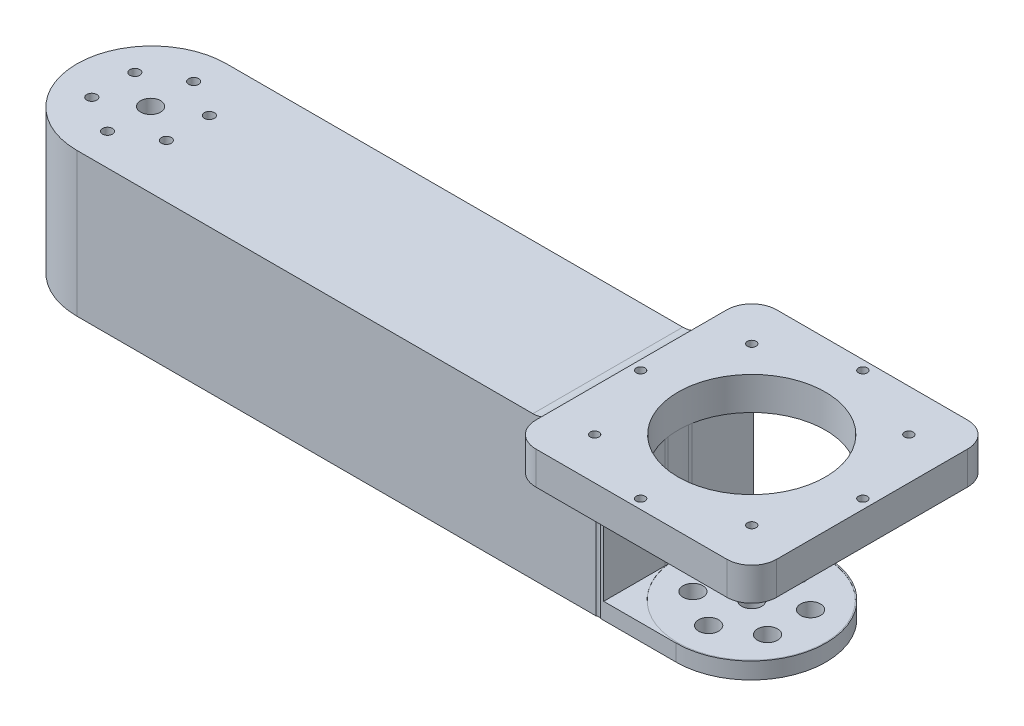
SolidWorks part; units mm, degrees
ref_plane "前视基准面" through (0, 0, 0) normal (0, 0, 1) x (1, 0, 0)
ref_plane "上视基准面" through (0, 0, 0) normal (0, 1, 0) x (1, 0, 0)
ref_plane "右视基准面" through (0, 0, 0) normal (1, 0, 0) x (0, 0, -1)
sketch "草图1" plane through (0, 0, 0) normal (0, 1, 0) x (1, 0, 0)
  line L0 (0, 0) -> (300, 0)
  line L1 (300, 0) -> (300, -60)
  line L2 (300, -60) -> (0, -60)
  line L3 (0, -60) -> (0, 0)
  dimension "D1" = 60
  dimension "D2" = 300
extrude "凸台-拉伸1" add sketch "草图1" along normal blind 57.52
fillet "圆角1" 2 edges at (0, 28.76, 0) (0, 28.76, 60) type full round first side face at (150, 28.76, 0) second side face at (150, 28.76, 60) middle face at (0, 28.76, 30)
sketch "草图3" plane through (300, 0, 0) normal (1, 0, 0) x (0, 0, -1)
  line L0 (0, 28.76) -> (-60, 28.76) construction
  line L1 (0, 57.52) -> (0, 0) construction
  line L2 (-60, 57.52) -> (-60, 0) construction
sketch "草图4" plane through (0, 57.52, 0) normal (0, 1, 0) x (1, 0, 0)
  circle A0 centre (29.5314, -29.9886) radius 29.5
  dimension "D1" = 59
sketch "草图9" plane through (300, 0, 0) normal (1, 0, 0) x (0, 0, -1)
  line L0 (-30, 57.52) -> (-30, 0) construction
  line L1 (-60, 57.52) -> (0, 57.52) construction
  line L2 (-60, 0) -> (0, 0) construction
  line L4 (-60, 50.92) -> (0, 50.92)
  line L5 (-60, 50.92) -> (-60, 6.6)
  line L6 (-60, 6.6) -> (0, 6.6)
  line L7 (0, 50.92) -> (0, 6.6)
  line L8 (-60, 50.92) -> (0, 6.6) construction
  line L9 (-60, 6.6) -> (0, 50.92) construction
  point P6 (-30, 28.76)
  dimension "D1" = 60
  dimension "D2" = 44.32
extrude "切除-拉伸5" cut sketch "草图9" against normal blind 59
fillet "圆角2" 2 edges at (300, 54.22, 60) (300, 54.22, 0) type full round first side face at (217.75, 28.76, 60) second side face at (217.75, 28.76, 0) middle face at (300, 54.22, 30)
fillet "圆角3" 2 edges at (300, 3.3, 60) (300, 3.3, 0) type full round first side face at (210.25, 28.76, 60) second side face at (210.25, 28.76, 0) middle face at (300, 3.3, 30)
sketch "草图10" plane through (0, 57.52, 0) normal (0, 1, 0) x (1, 0, 0)
  circle A0 centre (270.1322, -30.0374) radius 29.5
extrude "切除-拉伸6" cut sketch "草图10" against normal blind 51
fillet "圆角4" radius 10 2 edges at (241, 28.76, 25.3937) (241, 28.76, 34.6812)
sketch "草图16" plane through (0, 6.52, 0) normal (0, 1, 0) x (1, 0, 0)
  line L0 (300, -30) -> (240.6322, -30.0374) construction
  line L2 (300, 0) -> (300, -60) construction
  circle A0 centre (270.1322, -30.0374) radius 29.5 construction
  circle A1 centre (270.1322, -30.0374) radius 29.5 construction
  circle A2 centre (270.3161, -30.0187) radius 44.5 construction
  circle A3 centre (225.8161, -30.0187) radius 1.75
  dimension "D1" = 3.5
extrude "切除-拉伸8" cut sketch "草图16" along normal blind 115
ref_plane "基准面1" through (0, 57.52, 0) normal (0, 1, 0) x (1, 0, 0)
sketch "草图17" plane through (0, 57.52, 0) normal (0, 1, 0) x (1, 0, 0)
  line L0 (300, -30) -> (240.6322, -30.0374) construction
  line L1 (300, 0) -> (300, -60) construction
  line L2 (270.1322, -0.5374) -> (270, -60) construction
  line L4 (222.0661, 18.2313) -> (318.5661, 18.2313)
  line L5 (222.0661, 18.2313) -> (222.0661, -78.2687)
  line L6 (222.0661, -78.2687) -> (318.5661, -78.2687)
  line L7 (318.5661, 18.2313) -> (318.5661, -78.2687)
  line L8 (222.0661, 18.2313) -> (318.5661, -78.2687) construction
  line L9 (222.0661, -78.2687) -> (318.5661, 18.2313) construction
  circle A0 centre (270.1322, -30.0374) radius 29.5 construction
  circle A1 centre (270.1322, -30.0374) radius 29.5 construction
  point P11 (270.3161, -30.0187)
  dimension "D1" = 96.5
  dimension "D2" = 96.5
extrude "凸台-拉伸3" add sketch "草图17" along normal blind 6.6
sketch "草图18" plane through (0, 64.12, 0) normal (0, 1, 0) x (1, 0, 0)
  line L0 (222.0661, -30.0187) -> (318.5661, -30.0187) construction
  line L1 (222.0661, 18.2313) -> (222.0661, -78.2687) construction
  line L2 (318.5661, -78.2687) -> (318.5661, 18.2313) construction
  line L3 (270.3161, -30.0187) -> (270.3161, 18.2313) construction
  line L4 (318.5661, 18.2313) -> (222.0661, 18.2313) construction
  circle A0 centre (270.3161, -30.0187) radius 17.25 construction
  circle A1 centre (270.3161, -12.7687) radius 4
  circle A2 centre (285.255, -21.3937) radius 4
  circle A3 centre (285.255, -38.6437) radius 4
  circle A4 centre (270.3161, -47.2687) radius 4
  circle A5 centre (255.3772, -38.6437) radius 4
  circle A6 centre (255.3772, -21.3937) radius 4
  point P25 (270.3161, -30.0187)
  dimension "D1" = 34.5
  dimension "D2" = 6
  dimension "D3" = 8
sketch "草图19" plane through (0, 57.52, 0) normal (0, 1, 0) x (1, 0, 0)
  line L0 (270.3161, -78.2687) -> (270.3161, 18.2313) construction
  line L1 (222.0661, -78.2687) -> (318.5661, -78.2687) construction
  line L2 (318.5661, 18.2313) -> (222.0661, 18.2313) construction
extrude "切除-拉伸9" cut sketch "草图18" against normal blind 113.6
sketch "草图20" plane through (0, 64.12, 0) normal (0, 1, 0) x (1, 0, 0)
  line L0 (270.3161, -78.2687) -> (270.3161, 18.2313) construction
  circle A0 centre (270.3161, -30.0187) radius 44.5 construction
  circle A1 centre (270.3161, 14.4813) radius 1.75
  circle A2 centre (301.7824, 1.4475) radius 1.75
  circle A3 centre (314.8161, -30.0187) radius 1.75
  circle A4 centre (301.7824, -61.485) radius 1.75
  circle A5 centre (270.3161, -74.5187) radius 1.75
  circle A6 centre (238.8498, -61.485) radius 1.75
  circle A7 centre (225.8161, -30.0187) radius 1.75
  circle A8 centre (238.8498, 1.4475) radius 1.75
  point P23 (270.3161, -30.0187)
  dimension "D1" = 3.5
  dimension "D2" = 8
extrude "切除-拉伸10" cut sketch "草图20" against normal blind 109
sketch "草图21" plane through (0, 64.12, 0) normal (0, 1, 0) x (1, 0, 0)
  line L0 (270.3161, -78.2687) -> (270.3161, 18.2313) construction
  circle A0 centre (270.3161, -30.0187) radius 29.5
  dimension "D1" = 59
extrude "切除-拉伸11" cut sketch "草图21" against normal blind 27
ref_plane "基准面4" through (0, 50.92, 0) normal (0, -1, 0) x (-1, 0, 0)
sketch "草图24" plane through (0, 50.92, 0) normal (0, -1, 0) x (-1, 0, 0)
  line L2 (-222.0661, 18.2313) -> (-318.5661, 18.2313)
  line L3 (-222.0661, 18.2313) -> (-222.0661, -78.2687)
  line L4 (-222.0661, -78.2687) -> (-318.5661, -78.2687)
  line L5 (-318.5661, 18.2313) -> (-318.5661, -78.2687)
  line L6 (-222.0661, 18.2313) -> (-318.5661, -78.2687) construction
  line L7 (-222.0661, -78.2687) -> (-318.5661, 18.2313) construction
  circle A0 centre (-270.3161, -30.0187) radius 29.5
  dimension "D1" = 59
extrude "凸台-拉伸5" add sketch "草图24" against normal blind 10
sketch "草图25" plane through (0, 50.92, 0) normal (0, -1, 0) x (-1, 0, 0)
  line L0 (-300, -30) -> (-270.3161, -30.0187) construction
  line L1 (-300, 0) -> (-300, -60) construction
  line L2 (-270.3161, -78.2687) -> (-270.3161, 18.2313) construction
  circle A0 centre (-270.3161, -30.0187) radius 44.5 construction
  circle A1 centre (-314.8161, -30.0187) radius 1.75
  circle A2 centre (-301.7824, 1.4475) radius 1.75
  circle A3 centre (-270.3161, 14.4813) radius 1.75
  circle A4 centre (-238.8498, 1.4475) radius 1.75
  circle A5 centre (-225.8161, -30.0187) radius 1.75
  circle A6 centre (-238.8498, -61.485) radius 1.75
  circle A7 centre (-270.3161, -74.5187) radius 1.75
  circle A8 centre (-301.7824, -61.485) radius 1.75
  point P26 (-270.3161, -30.0187)
  dimension "D1" = 3.5
  dimension "D2" = 8
extrude "切除-拉伸12" cut sketch "草图25" against normal blind 28
sketch "草图26" plane through (0, 57.52, 0) normal (0, 1, 0) x (1, 0, 0)
  circle A0 centre (29.5314, -29.9886) radius 4
extrude "切除-拉伸13" cut sketch "草图26" against normal blind 81
sketch "草图27" plane through (0, 57.52, 0) normal (0, 1, 0) x (1, 0, 0)
  circle A0 centre (29.5314, -29.9886) radius 17.25 construction
  circle A1 centre (29.5314, -12.7386) radius 2
  circle A2 centre (44.4704, -21.3636) radius 2
  circle A3 centre (44.4704, -38.6136) radius 2
  circle A4 centre (29.5314, -47.2386) radius 2
  circle A5 centre (14.5925, -38.6136) radius 2
  circle A6 centre (14.5925, -21.3636) radius 2
  point P18 (29.5314, -29.9886)
  dimension "D1" = 34.5
  dimension "D2" = 6
extrude "切除-拉伸14" cut sketch "草图27" against normal up to surface (57.52 mm away) up to face at (29.5314, 0, 25.9886)
sketch "草图28" plane through (0, 0, 0) normal (0, -1, 0) x (-1, 0, 0)
  line L0 (-29.5314, -29.9886) -> (-300, -30) construction
  line L1 (-300, 0) -> (-300, -60) construction
  line L2 (-270.3161, -12.7687) -> (-270.3161, -47.2687) construction
  circle A0 centre (-270.3161, -30.0187) radius 4
extrude "切除-拉伸15" cut sketch "草图28" against normal up to surface (6.52 mm away) contours A0 up to face at (270.3161, 6.52, 16.7687)
fillet "圆角5" radius 10 1 edges at (222.0661, 57.52, -18.2313) type face fillet first side face at (270.3161, 57.52, -18.2313) second side face at (222.0661, 55.87, 30.0094)
fillet "圆角6" radius 10 1 edges at (318.5661, 57.52, -18.2313) type face fillet first side face at (275.3161, 57.52, -18.2313) second side face at (318.5661, 57.52, 30.0187)
fillet "圆角7" radius 10 1 edges at (318.5661, 57.52, 78.2687) type face fillet first side face at (318.5661, 57.52, 35.0187) second side face at (270.3161, 57.52, 78.2687)
fillet "圆角8" radius 10 1 edges at (222.0661, 57.52, 78.2687) type face fillet first side face at (265.3161, 57.52, 78.2687) second side face at (222.0661, 55.87, 32.5094)
fillet "圆角10" radius 10 1 edges at (222.0661, 57.52, 30)
